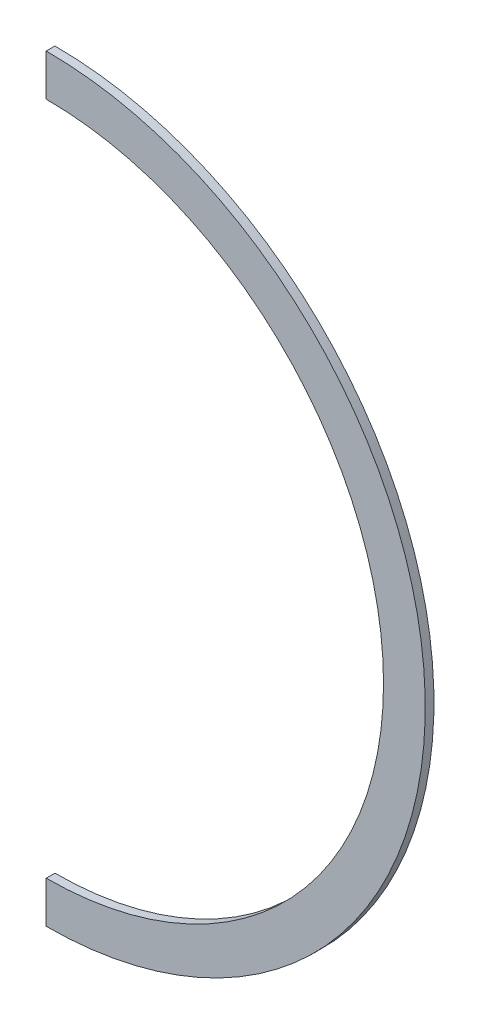
SolidWorks part; units mm, degrees
material "Balsa"
ref_plane "Front Plane" through (0, 0, 0) normal (0, 0, 1) x (1, 0, 0)
ref_plane "Top Plane" through (0, 0, 0) normal (0, 1, 0) x (1, 0, 0)
ref_plane "Right Plane" through (0, 0, 0) normal (1, 0, 0) x (0, 0, -1)
sketch "Sketch1" plane through (0, 0, 0) normal (0, 0, 1) x (1, 0, 0)
  line L0 (0, 32.094) -> (0, -346.2619) construction
  line L1 (0, 0) -> (0, 244.345) construction
  line L2 (0, 0) -> (0, 471.6969) construction
  line L3 (0, 0) -> (-283.5939, 0) construction
  line L4 (-127.2933, -32.5553) -> (-85.9841, -73.8644)
  line L5 (-85.9841, -73.8644) -> (-85.9841, -86.6438)
  line L6 (-85.9841, -73.8644) -> (-54.3993, -105.4493) construction
  arc A0 (-54.3993, -105.4493) -> (-127.2933, -32.5553) centre (0, 21.844) ccw
  arc A2 (-82.075, -89.6305) -> (-54.3993, -105.4493) centre (0, 21.844) ccw construction
  arc A3 (-127.2933, -32.5553) -> (-82.075, -89.6305) centre (0, 21.844) ccw construction
  arc A4 (-85.9841, -86.6438) -> (-54.3993, -105.4493) centre (0, 21.844) ccw
  spline S2 degree 3 poles (-19.218, -1838.2141) (276.9397, -392.4777) (232.9593, 72.7514) (49.9381, 150.9258) (45.7097, 152.4909) (37.1079, 155.2035) (32.7346, 156.3511) (27.1752, 157.5183) (26.0587, 157.7384) (23.8163, 158.1514) (22.6888, 158.3447) (19.306, 158.8811) (17.0511, 159.1813) (10.2867, 159.9126) (1.2693, 160.4377) (-7.745, 160.0789) (-14.5046, 159.4749) (-16.7575, 159.2176) (-20.1367, 158.7464) (-21.263, 158.5751) (-23.5156, 158.2037) (-24.6421, 158.0036) (-30.2426, 156.9366) (-34.6466, 155.8674) (-43.3063, 153.3113) (-47.562, 151.8242) (-55.9254, 148.4331) (-60.0331, 146.529) (-66.0807, 143.3516) (-68.0818, 142.2359) (-72.0044, 139.9197) (-73.9301, 138.7173) (-79.6017, 134.9792) (-86.884, 129.6473) (-93.6143, 123.6295) (-98.4521, 118.8554) (-100.0296, 117.2204) (-102.3424, 114.7015) (-103.1054, 113.8496) (-104.6077, 112.1297) (-105.3467, 111.2623) (-108.9818, 106.8875) (-111.6981, 103.2683) (-116.7574, 95.7975) (-119.1004, 91.9459) (-123.4121, 84.0098) (-125.3809, 79.9253) (-127.6006, 74.6695) (-128.0327, 73.61) (-128.8681, 71.4874) (-129.2719, 70.423) (-130.4422, 67.2205) (-131.1674, 65.0732) (-133.1812, 58.5951) (-135.4347, 49.861) (-136.834, 40.9354) (-137.5569, 34.168) (-137.7434, 31.9) (-137.9397, 28.4793) (-137.9911, 27.3374) (-138.0656, 25.0596) (-138.0887, 23.9223) (-138.135, 18.2442) (-137.9496, 13.7276) (-137.1441, 4.7454) (-136.5239, 0.2797) (-134.8456, -8.6005) (-133.7876, -13.015) (-131.2181, -21.791) (-129.7278, -26.0794) (-126.351, -34.4622) (-124.4643, -38.5569) (-120.2966, -46.5538) (-118.0156, -50.456) (-114.9122, -55.2108) (-114.2789, -56.1556) (-112.9868, -58.0327) (-112.3272, -58.9661) (-110.315, -61.7398) (-108.9333, -63.5482) (-104.6702, -68.8537) (-98.6716, -75.6089) (-92.0553, -81.7381) (-86.8592, -86.0978) (-85.0881, -87.5114) (-82.3719, -89.5716) (-81.4566, -90.2482) (-79.6058, -91.5811) (-78.6696, -92.238) (117.1329, -226.0075) (630.1685, 154.3992) (1500.4507, 1111.3958) knots -1.313799 -1.313799 -1.313799 -1.313799 0.03125 0.03125 0.0625 0.0625 0.09375 0.09375 0.101563 0.101563 0.109375 0.109375 0.125 0.125 0.15625 0.1875 0.1875 0.203125 0.203125 0.210937 0.210937 0.21875 0.21875 0.25 0.25 0.28125 0.28125 0.3125 0.3125 0.328125 0.328125 0.34375 0.34375 0.375 0.40625 0.40625 0.421875 0.421875 0.429687 0.429687 0.4375 0.4375 0.46875 0.46875 0.5 0.5 0.53125 0.53125 0.539062 0.539062 0.546875 0.546875 0.5625 0.5625 0.59375 0.625 0.625 0.640625 0.640625 0.648437 0.648437 0.65625 0.65625 0.6875 0.6875 0.71875 0.71875 0.75 0.75 0.78125 0.78125 0.8125 0.8125 0.84375 0.84375 0.851562 0.851562 0.859375 0.859375 0.875 0.875 0.90625 0.9375 0.9375 0.953125 0.953125 0.960937 0.960937 0.96875 0.96875 2.582348 2.582348 2.582348 2.582348 only from (66.3397, 143.1887) to (-66.0465, -100.0388)
  spline S3 degree 3 poles (66.3397, 143.1887) (62.3323, 145.3909) (58.2494, 147.3758) (49.9381, 150.9258) (45.7097, 152.4909) (37.1079, 155.2035) (32.7346, 156.3511) (27.1752, 157.5183) (26.0587, 157.7384) (23.8163, 158.1514) (22.6888, 158.3447) (19.306, 158.8811) (17.0511, 159.1813) (10.2867, 159.9126) (1.2693, 160.4377) (-7.745, 160.0789) (-14.5046, 159.4749) (-16.7575, 159.2176) (-20.1367, 158.7464) (-21.263, 158.5751) (-23.5156, 158.2037) (-24.6421, 158.0036) (-30.2426, 156.9366) (-34.6466, 155.8674) (-43.3063, 153.3113) (-47.562, 151.8242) (-55.9254, 148.4331) (-60.0331, 146.529) (-66.0807, 143.3516) (-68.0818, 142.2359) (-72.0044, 139.9197) (-73.9301, 138.7173) (-79.6017, 134.9792) (-86.884, 129.6473) (-93.6143, 123.6295) (-98.4521, 118.8554) (-100.0296, 117.2204) (-102.3424, 114.7015) (-103.1054, 113.8496) (-104.6077, 112.1297) (-105.3467, 111.2623) (-108.9818, 106.8875) (-111.6981, 103.2683) (-116.7574, 95.7975) (-119.1004, 91.9459) (-123.4121, 84.0098) (-125.3809, 79.9253) (-127.6006, 74.6695) (-128.0327, 73.61) (-128.8681, 71.4874) (-129.2719, 70.423) (-130.4422, 67.2205) (-131.1674, 65.0732) (-133.1812, 58.5951) (-135.4347, 49.861) (-136.834, 40.9354) (-137.5569, 34.168) (-137.7434, 31.9) (-137.9397, 28.4793) (-137.9911, 27.3374) (-138.0656, 25.0596) (-138.0887, 23.9223) (-138.135, 18.2442) (-137.9496, 13.7276) (-137.1441, 4.7454) (-136.5239, 0.2797) (-134.8456, -8.6005) (-133.7876, -13.015) (-131.2181, -21.791) (-129.7278, -26.0794) (-127.6847, -31.1513) (-127.3213, -32.0275) (-126.9491, -32.8995) knots 0 0 0 0 0.03125 0.03125 0.0625 0.0625 0.09375 0.09375 0.101563 0.101563 0.109375 0.109375 0.125 0.125 0.15625 0.1875 0.1875 0.203125 0.203125 0.210937 0.210937 0.21875 0.21875 0.25 0.25 0.28125 0.28125 0.3125 0.3125 0.328125 0.328125 0.34375 0.34375 0.375 0.40625 0.40625 0.421875 0.421875 0.429687 0.429687 0.4375 0.4375 0.46875 0.46875 0.5 0.5 0.53125 0.53125 0.539062 0.539062 0.546875 0.546875 0.5625 0.5625 0.59375 0.625 0.625 0.640625 0.640625 0.648437 0.648437 0.65625 0.65625 0.6875 0.6875 0.71875 0.71875 0.75 0.75 0.78125 0.78125 0.787815 0.787815 0.787815 0.787815 construction
  point P2 (0, 160.2226)
  point P3 (0, -116.9127)
  point P23 (-85.9841, -73.8644)
  dimension "D1" = 277.1353
  dimension "D2" = 276.86
  dimension "D3" = 21.844
  dimension "D5" = 45
  dimension "D6" = 113.03
  dimension "D4" = 58.42
  dimension "D7" = 45
extrude "Boss-Extrude1" add sketch "Sketch1" along normal mid plane 3.175
sketch "Sketch2" plane through (0, 0, 1.5875) normal (0, 0, 1) x (1, 0, 0)
  line L4 (-114.3729, -23.9231) -> (-70.7441, -67.5518)
  line L5 (-70.7441, -67.5518) -> (-70.7441, -79.0076)
  line L6 (-114.3729, -23.9231) -> (-70.7441, -67.5518)
  line L7 (-70.7441, -67.5518) -> (-70.7441, -79.0076)
  arc A2 (-70.7441, -79.0076) -> (-114.3729, -23.9231) centre (0, 21.844) ccw
  arc A3 (-70.7441, -79.0076) -> (-114.3729, -23.9231) centre (0, 21.844) ccw
  dimension "D1" = 15.24
extrude "Cut-Extrude1" cut sketch "Sketch2" against normal up to surface (3.175 mm away) up to face at (-27.5361, -9.1994, -1.5875)
fillet "Fillet1" radius 8.89 6 edges at (-127.2933, -32.5553, 0) (-114.3729, -23.9231, 0) (-85.9841, -73.8644, 0) (-85.9841, -86.6438, 0) (-70.7441, -67.5518, 0) (-70.7441, -79.0076, 0)
sketch "Sketch3" plane through (0, 0, 1.5875) normal (0, 0, 1) x (1, 0, 0)
  line L0 (0, 49.992) -> (0, 733.2) construction
  line L1 (0, 49.992) -> (0, 733.2) construction
  line L2 (-136.2041, -28.3557) -> (0, 49.992) construction
  line L3 (136.2041, -28.3557) -> (0, 49.992) construction
  line L4 (-136.2041, -28.3557) -> (0, 49.992) construction
  line L5 (136.2041, -28.3557) -> (0, 49.992) construction
  line L6 (-1.651, 152.6442) -> (-1.651, 160.2642)
  line L7 (1.651, 152.6442) -> (1.651, 160.2642)
  line L8 (-1.651, 152.6442) -> (1.651, 152.6442)
  line L9 (119.8454, -45.9681) -> (106.751, -38.3801)
  line L10 (121.4405, -43.2127) -> (108.3453, -35.6242)
  line L11 (-126.0584, -33.7901) -> (-88.588, -71.2606)
  line L12 (-85.9841, -77.5468) -> (-85.9841, -82.2574)
  line L13 (-126.0584, -33.7901) -> (-88.588, -71.2606) construction
  line L14 (-85.9841, -77.5468) -> (-85.9841, -82.2574) construction
  line L18 (121.4405, -43.2127) -> (108.3453, -35.6242)
  line L30 (-123.167, -47.8929) -> (-104.8722, -37.2914)
  line L35 (119.8454, -45.9681) -> (106.751, -38.3801)
  line L47 (108.5244, -35.721) -> (120.1169, -46.1175) construction
  line L48 (114.3206, -40.9193) -> (126.5619, -48.0121) construction
  line L49 (113.8577, -42.5592) -> (122.0137, -47.2849)
  line L50 (115.5132, -39.7021) -> (123.6691, -44.4278)
  line L51 (113.8577, -42.5592) -> (115.5132, -39.7021)
  line L52 (122.0137, -47.2849) -> (123.6691, -44.4278)
  line L58 (-124.7703, -45.1423) -> (-106.4681, -34.5364)
  line L59 (-124.7703, -45.1423) -> (-123.167, -47.8929)
  line L71 (-124.7703, -45.1423) -> (-123.167, -47.8929) construction
  line L72 (-124.7703, -45.1423) -> (-106.4681, -34.5364) construction
  line L73 (-123.167, -47.8929) -> (-104.8722, -37.2914) construction
  line L74 (-123.167, -47.8929) -> (-107.9499, -35.3951) construction
  line L75 (-115.5584, -41.644) -> (-110.9064, -38.9482) construction
  line L76 (-119.3826, -41.9518) -> (-112.6266, -38.0369)
  line L77 (-117.727, -44.8088) -> (-110.971, -40.8938)
  line L78 (-119.3826, -41.9518) -> (-117.727, -44.8088)
  line L79 (-112.6266, -38.0369) -> (-110.971, -40.8938)
  arc A0 (-54.3993, -105.4493) -> (-127.2933, -32.5553) centre (0, 21.844) ccw construction
  arc A2 (-1.651, 160.2642) -> (-130.2816, -24.9489) centre (0, 21.844) ccw construction
  arc A3 (-130.2816, -24.9489) -> (-127.2933, -32.5553) centre (0, 21.844) ccw construction
  arc A4 (-1.651, 160.2642) -> (-130.2816, -24.9489) centre (0, 21.844) ccw construction
  arc A5 (-130.2816, -24.9489) -> (-127.9919, -30.8906) centre (0, 21.844) ccw construction
  arc A6 (-82.3849, -89.4016) -> (-127.9919, -30.8906) centre (0, 21.844) ccw
  arc A7 (-127.9919, -30.8906) -> (-126.0584, -33.7901) centre (-119.7722, -27.504) ccw
  arc A8 (-85.9841, -77.5468) -> (-88.588, -71.2606) centre (-94.8741, -77.5468) ccw
  arc A9 (-85.9841, -82.2574) -> (-82.3849, -89.4016) centre (-77.0941, -82.2574) ccw
  arc A11 (-127.9919, -30.8906) -> (-126.0584, -33.7901) centre (-119.7722, -27.504) ccw construction
  arc A12 (-85.9841, -77.5468) -> (-88.588, -71.2606) centre (-94.8741, -77.5468) ccw construction
  arc A13 (-85.9841, -82.2574) -> (-82.3849, -89.4016) centre (-77.0941, -82.2574) ccw construction
  arc A14 (130.2816, -24.9489) -> (1.651, 160.2642) centre (0, 21.844) ccw construction
  arc A15 (1.651, 160.2642) -> (-1.651, 160.2642) centre (0, 21.844) ccw
  arc A16 (130.2816, -24.9489) -> (1.651, 160.2642) centre (0, 21.844) ccw construction
  arc A17 (1.651, 160.2642) -> (-1.651, 160.2642) centre (0, 21.844) ccw
  spline S0 degree 3 poles (106.751, -38.3801) (107.2824, -37.4615) (107.8139, -36.5429) (108.3453, -35.6242) knots 0 0 0 0 1 1 1 1 weights 1 1 1 1
  spline S1 degree 3 poles (119.8454, -45.9681) (120.3771, -45.0496) (120.9088, -44.1312) (121.4405, -43.2127) knots 0 0 0 0 1 1 1 1 weights 1 1 1 1
  spline S2 degree 3 poles (-885.9994, -1769.7518) (-211.5637, -622.999) (457.4594, 532.6422) (1115.3785, 1687.342) knots -628.025775 -628.025775 -628.025775 -628.025775 629.321979 629.321979 629.321979 629.321979 weights 1.00213 0.999289 0.99929 1.002132 only from (119.8454, -45.9681) to (121.4405, -43.2127)
  spline S3 degree 3 poles (-1102.9631, 1696.4301) (-441.8977, 540.8873) (227.2766, -614.259) (901.0121, -1762.8827) knots -628.210575 -628.210575 -628.210575 -628.210575 629.142222 629.142222 629.142222 629.142222 weights 1.001328 0.999558 0.999557 1.001327 only from (-106.4681, -34.5364) to (-104.8722, -37.2914)
  spline S4 degree 3 poles (-106.4681, -34.5364) (-105.9361, -35.4547) (-105.4042, -36.373) (-104.8722, -37.2914) knots 0 0 0 0 1 1 1 1 weights 1 1 1 1 construction
  spline S6 degree 3 poles (-898.488, -1762.9922) (-224.3423, -615.0332) (444.2888, 540.7284) (1102.2727, 1695.4214) knots -627.922326 -627.922326 -627.922326 -627.922326 629.425989 629.425989 629.425989 629.425989 weights 1.001921 0.999359 0.99936 1.001924 only from (106.751, -38.3801) to (108.3453, -35.6242)
  point P49 (-116.0256, -43.8229)
  point P50 (120.451, -46.3794)
  arc M19 (-82.3849, -89.4016) -> (-127.9919, -30.8906) centre (0, 21.844) ccw
  line M21 (-126.0584, -33.7901) -> (-88.588, -71.2606)
  dimension "D1" = 3.302
  dimension "D2" = 7.62
  dimension "D4" = 3.302
  dimension "D5" = 7.62
  dimension "D6" = 3.302
  dimension "D7" = 5.842
  dimension "D3" = 0
extrude "Cut-Extrude2" [suppressed] cut sketch "Sketch3" against normal through all contours L79 L76 L77 M21 | L6 L8 L7 M19 | L51 L49 L50 M19
sketch "Sketch4" plane through (0, 0, 0) normal (1, 0, 0) x (0, 0, -1)
  line L1 (-96.2805, 232.7957) -> (122.2438, 232.7957)
  line L2 (-96.2805, 232.7957) -> (-96.2805, -207.8589)
  line L3 (-96.2805, -207.8589) -> (122.2438, -207.8589)
  line L4 (122.2438, 232.7957) -> (122.2438, -207.8589)
extrude "Cut-Extrude3" cut sketch "Sketch4" against normal through all
equation "\"a\"= 0.06"
equation "\"slotwidth\"=0.13"
equation "\"slotheight\"=0.3"
